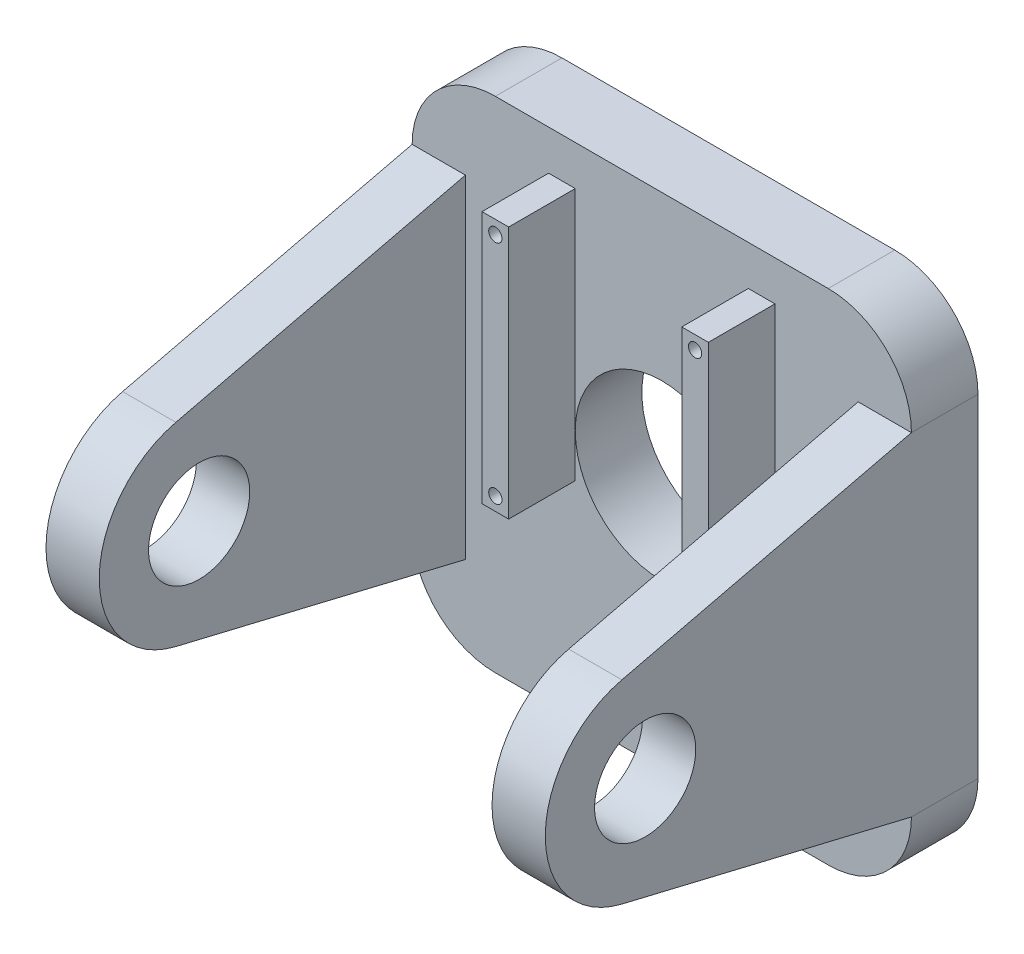
SolidWorks part; units mm, degrees
material "6061 Alloy"
ref_plane "Front Plane" through (0, 0, 0) normal (1, 0, 0) x (0, 1, 0)
ref_plane "Top Plane" through (0, 0, 0) normal (0, 0, 1) x (0, 1, 0)
ref_plane "Right Plane" through (0, 0, 0) normal (0, 1, 0) x (-1, 0, 0)
sketch "Sketch1" plane through (0, 0, 0) normal (0, 0, 1) x (0, 1, 0)
  line L1 (-25, -37.5) -> (25, -37.5)
  line L2 (-37.5, -25) -> (-37.5, 25)
  line L3 (-25, 37.5) -> (25, 37.5)
  line L4 (37.5, -25) -> (37.5, 25)
  line L5 (-37.5, -37.5) -> (37.5, 37.5) construction
  line L6 (-37.5, 37.5) -> (37.5, -37.5) construction
  arc A0 (-25, -37.5) -> (-37.5, -25) centre (-25, -25) cw
  arc A1 (25, -37.5) -> (37.5, -25) centre (25, -25) ccw
  arc A2 (25, 37.5) -> (37.5, 25) centre (25, 25) cw
  arc A3 (-37.5, 25) -> (-25, 37.5) centre (-25, 25) cw
  point P0 (0, 0)
  dimension "D2" = 12.5
  dimension "D1" = 75
extrude "Boss-Extrude1" add sketch "Sketch1" along normal blind 10
sketch "Sketch2" plane through (37.5, 0, 0) normal (1, 0, 0) x (0, 1, 0)
  line L0 (0, 50) -> (0, 0) construction
  line L1 (-25, 10) -> (25, 10) construction
  line L2 (-25, 10) -> (-14.5878, 53.4924)
  line L3 (25, 10) -> (14.5878, 53.4924)
  line L4 (25, 10) -> (25, 0) construction
  line L5 (37.5, 10) -> (25, 10) construction
  circle A0 centre (0, 50) radius 15
  circle A1 centre (0, 50) radius 7.6
  line M8 (25, 10) -> (-25, 10)
  dimension "D2" = 30
  dimension "D3" = 15.2
  dimension "D1" = 40
extrude "Boss-Extrude2" add sketch "Sketch2" against normal blind 8 contours L0 A0 L2 M8 | A0 L0 L3 M8 | A1 A0 region at (37.5, -11.4437, 40.9726) region at (37.5, 11.3969, 24.1864) region at (37.5, -11.3969, 24.1864)
mirror "Mirror1" about plane through (0, 0, 0) normal (1, 0, 0) of "Boss-Extrude2"
sketch "Sketch3" plane through (0, 0, 10) normal (0, 0, 1) x (1, 0, 0)
  line L0 (0, 37.5) -> (0, -37.5) construction
  line L1 (25, 37.5) -> (-25, 37.5) construction
  line L2 (-25, -37.5) -> (25, -37.5) construction
  circle A0 centre (0, 32.5) radius 1.6
  circle A1 centre (0, -32.5) radius 1.6
  dimension "D1" = 3.2
  dimension "D2" = 5
  dimension "D3" = 5
extrude "Cut-Extrude1" [suppressed] cut sketch "Sketch3" against normal through all
sketch "Sketch4" plane through (0, 0, 10) normal (0, 0, 1) x (1, 0, 0)
  circle A0 centre (0, 0) radius 13
  dimension "D1" = 26
extrude "Cut-Extrude2" cut sketch "Sketch4" against normal through all
sketch "Sketch5" plane through (0, 0, 10) normal (0, 0, 1) x (1, 0, 0)
  line L1 (-17, 31.5) -> (17, 31.5)
  line L2 (-17, 31.5) -> (-17, -6.5)
  line L3 (-17, -6.5) -> (17, -6.5)
  line L4 (17, 31.5) -> (17, -6.5)
  line L5 (-17, 31.5) -> (17, -6.5) construction
  line L6 (-17, -6.5) -> (17, 31.5) construction
  line L7 (-13, -6.5) -> (13, -6.5)
  line L8 (-13, -6.5) -> (-13, 31.5)
  line L9 (-13, 31.5) -> (13, 31.5)
  line L10 (13, -6.5) -> (13, 31.5)
  line L11 (-13, -6.5) -> (13, 31.5) construction
  line L12 (-13, 31.5) -> (13, -6.5) construction
  circle A0 centre (15, -4.5) radius 1
  circle A1 centre (-15, -4.5) radius 1
  circle A2 centre (-15, 29.5) radius 1
  circle A3 centre (15, 29.5) radius 1
  point P12 (0, 12.5)
  point P17 (0, 12.5)
  dimension "D1" = 2
  dimension "D3" = 2
  dimension "D5" = 2
  dimension "D2" = 2
  dimension "D4" = 2
  dimension "D7" = 4
extrude "Boss-Extrude3" add sketch "Sketch5" along normal blind 10 contours L3 L8 L1 L2 A2 A1 | L10 L3 L4 L1 A3 A0 region at (-15, 12.5, 10) region at (15, 12.5, 10)
